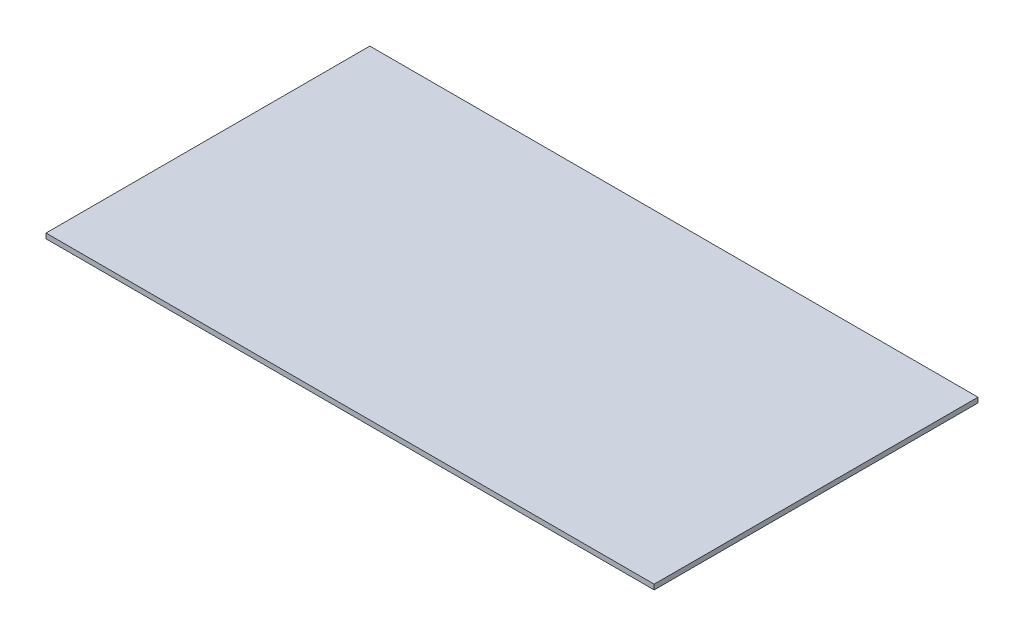
SolidWorks part; units mm, degrees
material "Mahogany"
ref_plane "Front Plane" through (0, 0, 0) normal (0, 0, 1) x (1, 0, 0)
ref_plane "Top Plane" through (0, 0, 0) normal (0, 1, 0) x (1, 0, 0)
ref_plane "Right Plane" through (0, 0, 0) normal (1, 0, 0) x (0, 0, -1)
sketch "Sketch1" plane through (0, 0, 0) normal (0, 1, 0) x (1, 0, 0)
  line L1 (770, -410) -> (-770, -410)
  line L2 (770, -410) -> (770, 410)
  line L3 (770, 410) -> (-770, 410)
  line L4 (-770, -410) -> (-770, 410)
  line L5 (770, -410) -> (-770, 410) construction
  line L6 (770, 410) -> (-770, -410) construction
  point P0 (0, 0)
  dimension "D1" = 1540
  dimension "D2" = 820
extrude "Boss-Extrude1" add sketch "Sketch1" along normal blind 12.7
equation "\"W\"= 1500"
equation "\"L\"= 780"
equation "\"H\"= 780"
equation "\"ARM_BOLT_SPACING\"= 166"
equation "\"ARM_TO_WALL\"= 200"
equation "\"D1@Sketch1\"=\"W\"+40"
equation "\"D2@Sketch1\"=\"L\"+40"
